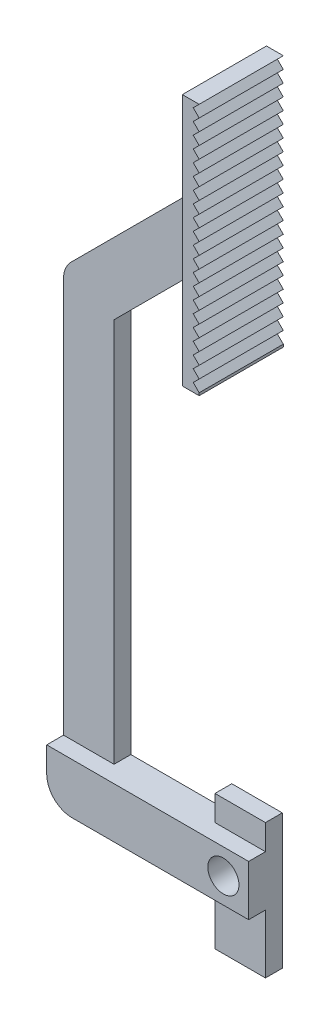
SolidWorks part; units mm, degrees
ref_plane "前视基准面" through (0, 0, 0) normal (0, 0, 1) x (1, 0, 0)
ref_plane "上视基准面" through (0, 0, 0) normal (0, 1, 0) x (1, 0, 0)
ref_plane "右视基准面" through (0, 0, 0) normal (1, 0, 0) x (0, 0, -1)
sketch "草图1" plane through (0, 0, 0) normal (0, 0, 1) x (1, 0, 0)
  line L0 (16, 6) -> (15, 6)
  line L2 (0, 0) -> (28, 0) construction
  line L3 (3, 3) -> (15, 3)
  line L4 (0, -3) -> (15, -3)
  line L5 (0, 0) -> (0, 40) construction
  line L6 (0, -55) -> (0, 55) construction
  line L9 (0, 0) -> (0, 50) construction
  line L13 (-3, 0) -> (-3, 50)
  line L14 (15, -3) -> (15, -10)
  line L15 (16, 6) -> (20, 6)
  line L17 (16, -10) -> (20, -10)
  line L19 (21, 3) -> (21, 6)
  line L20 (21, 3) -> (21, -3)
  line L21 (3, 3) -> (3, 48.7574)
  line L22 (20, 6) -> (21, 6)
  line L23 (15, 6) -> (15, 3)
  line L24 (15, -10) -> (20.5, -10)
  line L25 (20.5, -10) -> (21, -10)
  line L26 (21, -10) -> (21, -3)
  line L29 (0, 50) -> (6.347, 56.347) construction
  line L30 (0, 50) -> (13, 63) construction
  line L31 (-2.1213, 52.1213) -> (10.8787, 65.1213)
  line L32 (3, 48.7574) -> (15.1213, 60.8787)
  line L33 (10.8787, 65.1213) -> (15.1213, 69.364)
  line L34 (15.1213, 69.364) -> (15.1213, 60.8787)
  line L35 (3, 3) -> (-3, 3)
  arc A0 (-3, 0) -> (0, -3) centre (0, 0) ccw
  arc A2 (-3, 0) -> (0, -3) centre (0, 0) ccw
  circle A7 centre (18, 0) radius 1.85
  arc A10 (-3, 0) -> (0, -3) centre (0, 0) ccw
  arc A12 (-2.1213, 52.1213) -> (-3, 50) centre (0, 50) ccw
  arc A14 (-2.1213, 52.1213) -> (-3, 50) centre (0, 50) ccw
  point P2 (14, 0)
  point P7 (0, 25)
  point P10 (0, 20)
  point P19 (6.5, 46.5)
  point P26 (6.5, 56.5)
  dimension "D1" = 13
  dimension "D2" = 13
extrude "凸台-拉伸1" add sketch "草图1" along normal mid plane 4 contours A0 L4 L17 L15 L3 region at (11.4311, -0.9801, 0)
sketch "草图4" plane through (0, 0, 2) normal (0, 0, 1) x (1, 0, 0)
  line L1 (15, 3) -> (21, 3)
  line L2 (15, 3) -> (15, 6)
  line L3 (15, 6) -> (21, 6)
  line L4 (21, 3) -> (21, 6)
  line L5 (15, -3) -> (21, -3)
  line L6 (15, -3) -> (15, -10)
  line L7 (15, -10) -> (21, -10)
  line L8 (21, -3) -> (21, -10)
extrude "切除-拉伸2" cut sketch "草图4" against normal blind 2
extrude "凸台-拉伸2" add sketch "草图1<3>" against normal blind 2 contours L31 A12 L13 L35 L21 L32 L34 L33 region at (2.3175, 36.2665, 0)
sketch "草图1<3>" plane through (0, 0, 0) normal (0, 0, 1) x (1, 0, 0) same geometry as "草图1"
sketch "草图5" plane through (15.1213, 0, 0) normal (1, 0, 0) x (0, 0, -1)
  line L1 (-4, 80) -> (6, 80)
  line L2 (-4, 80) -> (-4, 50)
  line L3 (-4, 50) -> (6, 50)
  line L4 (6, 80) -> (6, 50)
  line L5 (-4, 80) -> (6, 50) construction
  line L6 (-4, 50) -> (6, 80) construction
  point P0 (1, 65)
extrude "凸台-拉伸3" add sketch "草图5" along normal blind 2
sketch "草图6" plane through (0, 0, 4) normal (0, 0, 1) x (1, 0, 0)
  line L0 (17.1213, 80) -> (16.4142, 79.2929)
  line L1 (16.4142, 79.2929) -> (17.1213, 78.5858)
  line L2 (17.1213, 80) -> (17.1213, 50) construction
  line L3 (17.1213, 78.5858) -> (17.1213, 80)
extrude "切除-拉伸3" cut sketch "草图6" against normal blind 10
pattern_linear "阵列(线性)1" count 21 spacing 1.414 along (0, -1, 0) of "切除-拉伸3"
